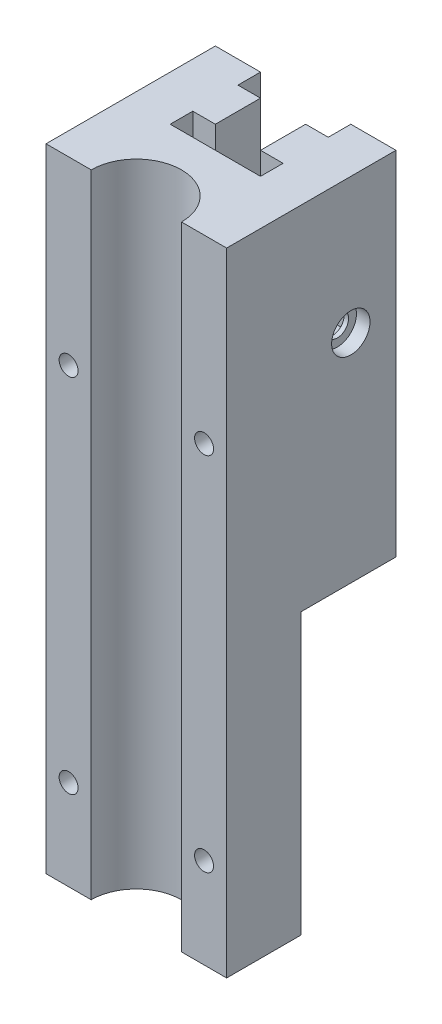
SolidWorks part; units mm, degrees
other "Markup1"
sketch "Sketch9" plane through (-20, 0, 37.5) normal (-0.6467, 0.1839, 0.7403) x (0.76, 0.0728, 0.6458)
ref_plane "Front Plane" through (0, 0, 0) normal (0, 0, 1) x (1, 0, 0)
ref_plane "Top Plane" through (0, 0, 0) normal (0, 1, 0) x (1, 0, 0)
ref_plane "Right Plane" through (0, 0, 0) normal (1, 0, 0) x (0, 0, -1)
sketch "Sketch1" plane through (0, 0, 0) normal (0, 1, 0) x (1, 0, 0)
  line L0 (10, 0) -> (-10, 0) construction
  line L1 (-10, 0) -> (-20, 0)
  line L2 (-20, 0) -> (-20, -37.5)
  line L3 (-20, -37.5) -> (20, -37.5)
  line L4 (20, -37.5) -> (20, 0)
  line L5 (20, 0) -> (10, 0)
  line L6 (10, 0) -> (10, -5)
  line L7 (10, -5) -> (5, -5)
  line L8 (5, -5) -> (5, -15)
  line L9 (5, -15) -> (10, -15)
  line L10 (10, -15) -> (10, -20)
  line L11 (10, -20) -> (-10, -20)
  line L12 (0, 0) -> (0, -20) construction
  line L13 (-10, 0) -> (-10, -5)
  line L14 (-10, -5) -> (-5, -5)
  line L15 (-5, -5) -> (-5, -15)
  line L16 (-5, -15) -> (-10, -15)
  line L17 (-10, -15) -> (-10, -20)
  line L18 (0, 0) -> (0, -37.5) construction
  circle A1 centre (0, -37.5) radius 10
  point P3 (0, 0)
  point P21 (0, -37.5)
  point P22 (0, -36.8779)
  dimension "D10" = 20
  dimension "D1" = 37.5
  dimension "D2" = 5
  dimension "D3" = 5
  dimension "D4" = 5
  dimension "D5" = 10
  dimension "D6" = 5
  dimension "D7" = 10
  dimension "D8" = 40
  dimension "D9" = 20
  dimension "D11" = 37.5
extrude "Boss-Extrude1" add sketch "Sketch1" against normal blind 140 contours A1 L3 L4 L5 L6 L7 L8 L9 L10 L11 L17 L16 L15 L14 L13 L1 L2 region at (-10.5483, 0, 2.5)
sketch "Sketch5" plane through (0, -140, 0) normal (0, -1, 0) x (1, 0, 0)
  line L0 (-20, 0) -> (-20, 37.5) construction
  line L1 (20, 0) -> (-20, 0)
  line L2 (20, 0) -> (20, 21)
  line L3 (20, 21) -> (-20, 21)
  line L4 (-20, 0) -> (-20, 21)
  dimension "D1" = 21
extrude "Cut-Extrude5" cut sketch "Sketch5" against normal blind 62
sketch "Sketch3" plane through (20, 0, 0) normal (1, 0, 0) x (0, 0, -1)
  line L0 (0, -78) -> (0, 0) construction
  line L1 (0, 0) -> (-20, 0)
  line L2 (0, 0) -> (0, -25)
  line L3 (0, -25) -> (-20, -25)
  line L4 (-20, 0) -> (-20, -25)
  line L5 (-20, -25) -> (0, -25)
  line L6 (-20, -25) -> (-20, -35)
  line L7 (-20, -35) -> (0, -35)
  line L8 (0, -25) -> (0, -35)
  line L9 (-15, -25) -> (-15, -35)
  line L10 (-5, -25) -> (-5, -35)
  line L11 (-10, -25) -> (-10, -35) construction
  line L12 (-15, -30) -> (-5, -30) construction
  line L13 (-37.5, 0) -> (0, 0) construction
  circle A0 centre (-10, -30) radius 2.5
  circle A1 centre (-10, -30) radius 4.25
  dimension "D6" = 5
  dimension "D7" = 8.5
  dimension "D1" = 20
  dimension "D2" = 0
  dimension "D3" = 10
  dimension "D4" = 5
  dimension "D5" = 10
  dimension "D9" = 25
extrude "Cut-Extrude2" cut sketch "Sketch3" against normal blind 30 and the other way blind 1 from offset 5 contours L10 L5 L9 L7 | A1 A0 | A0 region at (20, -30, 5.1414) region at (20, -30, 10) region at (20, -30, 14.1298) offset against normal yes
extrude "Cut-Extrude3" cut sketch "Sketch3<3>" against normal through all contours A0 region at (20, -30, 10)
sketch "Sketch3<3>" plane through (20, 0, 0) normal (1, 0, 0) x (0, 0, -1) same geometry as "Sketch3"
extrude "Cut-Extrude4" cut sketch "Sketch3<5>" against normal blind 3 contours A1 A0 region at (20, -30, 14.1298)
sketch "Sketch3<5>" plane through (20, 0, 0) normal (1, 0, 0) x (0, 0, -1) same geometry as "Sketch3"
mirror "Mirror1" about plane through (0, 0, 0) normal (1, 0, 0) of "Cut-Extrude4"
sketch "Sketch7" plane through (0, 0, 37.5) normal (0, 0, 1) x (1, 0, 0)
  line L0 (-20, -140) -> (-10, -140) construction
  line L1 (-10, -140) -> (-10, 0) construction
  line L2 (10, -140) -> (20, -140) construction
  line L3 (10, -140) -> (10, 0) construction
  line L4 (20, -140) -> (20, 0) construction
  line L5 (10, 0) -> (20, 0) construction
  line L6 (-20, 0) -> (-10, 0) construction
  line L7 (-20, -140) -> (-20, 0) construction
  line L8 (-20, -140) -> (-10, -140)
  line L9 (-10, -140) -> (-10, 0)
  line L10 (10, -140) -> (20, -140)
  line L11 (10, -140) -> (10, 0)
  line L12 (20, -140) -> (20, 0)
  line L13 (10, 0) -> (20, 0)
  line L14 (-20, 0) -> (-10, 0)
  line L15 (-20, -140) -> (-20, 0)
  line L16 (0, -140) -> (0, 0) construction
  line L17 (-10, 0) -> (10, 0)
  line L18 (-10, 0) -> (-10, -140)
  line L19 (-10, -140) -> (10, -140)
  line L20 (10, 0) -> (10, -140)
  line L21 (-15, 0) -> (-15, -140) construction
  line L22 (15, 0) -> (15, -140) construction
  circle A0 centre (-15, -120) radius 2.1
  circle A1 centre (15, -120) radius 2.1
  circle A2 centre (-15, -40) radius 2.1
  circle A3 centre (15, -40) radius 2.1
  dimension "D1" = 4.2
  dimension "D2" = 4.2
  dimension "D7" = 4.2
  dimension "D8" = 4.2
  dimension "D3" = 20
  dimension "D4" = 20
  dimension "D5" = 40
  dimension "D6" = 40
extrude "Cut-Extrude7" cut sketch "Sketch7" against normal blind 10 contours A2 | A3 | A1 | A0
